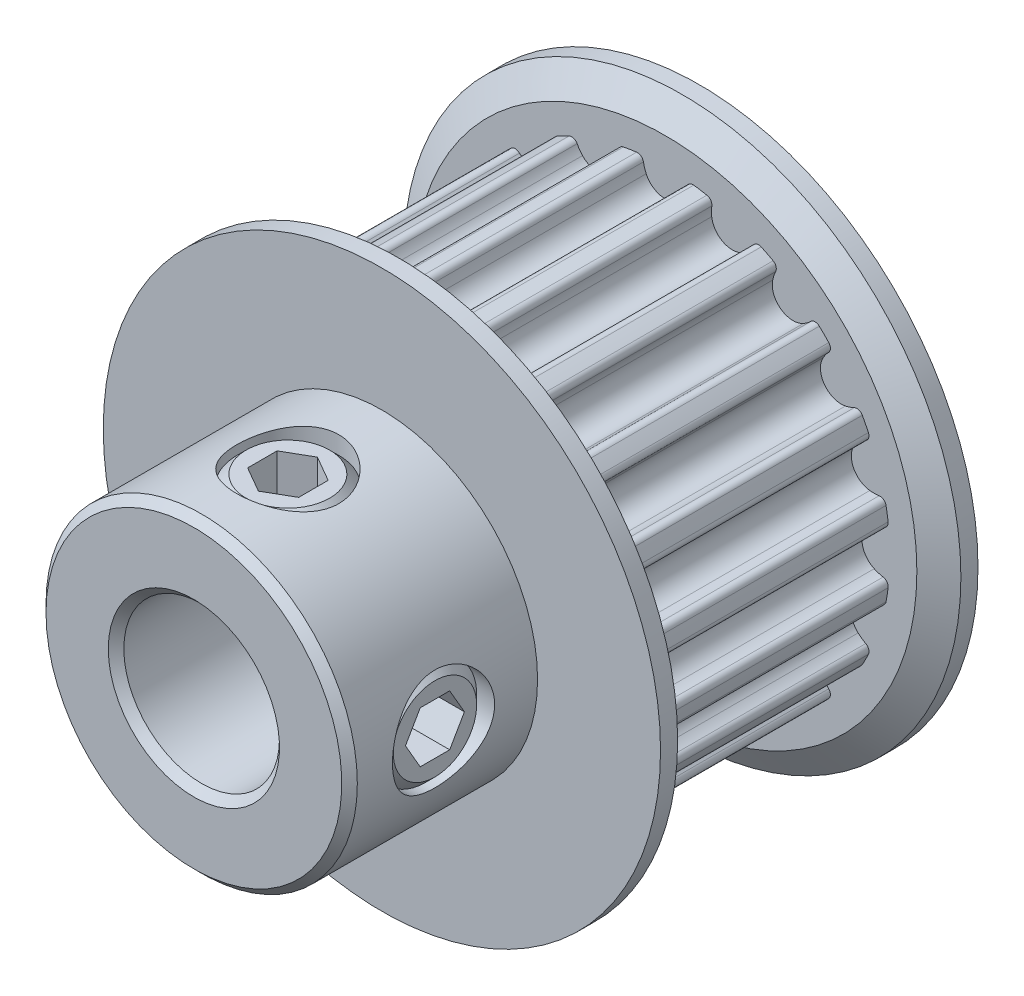
SolidWorks part; units mm, degrees
ref_plane "Front Plane" through (0, 0, 0) normal (0, 0, 1) x (1, 0, 0)
ref_plane "Top Plane" through (0, 0, 0) normal (0, 1, 0) x (1, 0, 0)
ref_plane "Right Plane" through (0, 0, 0) normal (1, 0, 0) x (0, 0, -1)
sketch "Sketch1" plane through (0, 0, 0) normal (0, 0, 1) x (1, 0, 0)
  line L1 (-2.6202, 8.0295) -> (2.6202, 8.0295) construction
  line L4 (0, 0) -> (0, 8.0295) construction
  line L5 (0, 8.0295) -> (0, 13.7072) construction
  line L6 (0, 9.5505) -> (2.9628, 9.0793) construction
  line L7 (2.9628, 9.0793) -> (4.0126, 8.7367) construction
  line L8 (2.9628, 9.0793) -> (2.6202, 8.0295) construction
  line L9 (-2.9628, 9.0793) -> (-2.6202, 8.0295) construction
  line L10 (-2.8446, 8.7171) -> (-3.7091, 11.3665)
  line L11 (-3.7091, 11.3665) -> (3.7091, 11.3665)
  line L12 (3.7091, 11.3665) -> (2.8446, 8.7171)
  circle A0 centre (0, 0) radius 9.5505 construction
  circle A1 centre (0, 0) radius 11.3665 construction
  circle A2 centre (0, 0) radius 9.1695 construction
  arc A3 (-0.7739, 8.5279) -> (0.7739, 8.5279) centre (0, 8.8795) ccw
  arc A4 (-0.7739, 8.5279) -> (-0.8866, 8.891) centre (0.61, 9.1566) cw
  arc A5 (-2.8446, 8.7171) -> (-1.1645, 9.0953) centre (0, 0) cw
  arc A6 (-0.8866, 8.891) -> (-1.1645, 9.0953) centre (-1.1328, 8.8473) ccw
  arc A7 (2.8446, 8.7171) -> (1.1645, 9.0953) centre (0, 0) ccw
  arc A8 (0.8866, 8.891) -> (1.1645, 9.0953) centre (1.1328, 8.8473) cw
  arc A9 (0.7739, 8.5279) -> (0.8866, 8.891) centre (-0.61, 9.1566) ccw
  point P6 (0, 20.9083)
  point P11 (0, 9.5505)
  point P13 (0, 11.3665)
  point P14 (0, 9.1695)
  dimension "D1" = 7.2012
  dimension "D2" = 4.1567
sketch "Sketch2" plane through (0, 0, 0) normal (1, 0, 0) x (0, 0, -1)
  line L0 (-10.31, 3.175) -> (10.31, 3.175)
  line L1 (-10.31, 3.175) -> (-10.31, 6.35)
  line L2 (-10.31, 6.35) -> (-2.64, 6.35)
  line L3 (-2.64, 6.35) -> (-2.64, 11.3665)
  line L4 (-2.64, 11.3665) -> (-1.245, 11.3665) construction
  line L5 (-1.245, 11.3665) -> (-1.245, 9.1695) construction
  line L6 (-1.245, 9.1695) -> (8.915, 9.1695)
  line L7 (8.915, 9.1695) -> (8.915, 11.3665) construction
  line L8 (8.915, 11.3665) -> (10.31, 11.3665) construction
  line L9 (10.31, 11.3665) -> (10.31, 3.175)
  line L10 (-10.31, 0) -> (10.31, 0) construction
  line L11 (9.6125, 11.3665) -> (8.915, 10.268)
  line L12 (-1.245, 10.268) -> (-1.9425, 11.3665)
  line L13 (-2.64, 11.3665) -> (-1.9425, 11.3665)
  line L14 (-1.245, 10.268) -> (-1.245, 9.1695)
  line L15 (8.915, 9.1695) -> (8.915, 10.268)
  line L16 (9.6125, 11.3665) -> (10.31, 11.3665)
  arc A0 (-1.245, 10.268) -> (-1.9425, 11.3665) centre (-2.4588, 10.268) ccw construction
  arc A1 (8.915, 10.268) -> (9.6125, 11.3665) centre (10.1288, 10.268) cw construction
  point P12 (-1.245, 10.268)
  point P14 (-1.9425, 11.3665)
  point P20 (8.915, 10.268)
  point P21 (9.6125, 11.3665)
  point P25 (8.915, 0)
  point P26 (-1.245, 0)
revolve "Revolve1" add sketch "Sketch2" angle 360 mid plane about L10
sketch "Sketch3" plane through (0, 0, 0) normal (0, 0, 1) x (1, 0, 0)
  line L6 (3.7091, 11.3665) -> (-3.7091, 11.3665)
  line L7 (2.8446, 8.7171) -> (3.7091, 11.3665)
  line L8 (-3.7091, 11.3665) -> (-2.8446, 8.7171)
  line L9 (3.7091, 11.3665) -> (-3.7091, 11.3665)
  line L10 (2.8446, 8.7171) -> (3.7091, 11.3665)
  line L11 (-3.7091, 11.3665) -> (-2.8446, 8.7171)
  arc A8 (2.8446, 8.7171) -> (1.1645, 9.0953) centre (0, 0) ccw
  arc A9 (1.1645, 9.0953) -> (0.8866, 8.891) centre (1.1328, 8.8473) ccw
  arc A10 (0.7739, 8.5279) -> (0.8866, 8.891) centre (-0.61, 9.1566) ccw
  arc A11 (-0.7739, 8.5279) -> (0.7739, 8.5279) centre (0, 8.8795) ccw
  arc A12 (-0.8866, 8.891) -> (-0.7739, 8.5279) centre (0.61, 9.1566) ccw
  arc A13 (-0.8866, 8.891) -> (-1.1645, 9.0953) centre (-1.1328, 8.8473) ccw
  arc A14 (-1.1645, 9.0953) -> (-2.8446, 8.7171) centre (0, 0) ccw
  arc A15 (2.8446, 8.7171) -> (1.1645, 9.0953) centre (0, 0) ccw
  arc A16 (1.1645, 9.0953) -> (0.8866, 8.891) centre (1.1328, 8.8473) ccw
  arc A17 (0.7739, 8.5279) -> (0.8866, 8.891) centre (-0.61, 9.1566) ccw
  arc A18 (-0.7739, 8.5279) -> (0.7739, 8.5279) centre (0, 8.8795) ccw
  arc A19 (-0.8866, 8.891) -> (-0.7739, 8.5279) centre (0.61, 9.1566) ccw
  arc A20 (-0.8866, 8.891) -> (-1.1645, 9.0953) centre (-1.1328, 8.8473) ccw
  arc A21 (-1.1645, 9.0953) -> (-2.8446, 8.7171) centre (0, 0) ccw
  dimension "D1" = 0
extrude "Cut-Extrude1" cut sketch "Sketch3" against normal up to vertex (8.915 mm away) from vertex up to point (0, 9.1695, -8.915) starting at point (0, 9.1695, 1.245)
pattern_circular "CirPattern1" count 20 over 360 about axis through (0, 0, 10.31) along (0, 0, 1) of "Cut-Extrude1"
sketch "Sketch4" plane through (0, 0, 0) normal (1, 0, 0) x (0, -1, 0)
  line L0 (0, -2.64) -> (0, -10.31) construction
  line L1 (-6.35, -2.64) -> (6.35, -2.64) construction
  line L2 (-6.35, -10.31) -> (6.35, -10.31) construction
  circle A0 centre (0, -6.475) radius 2.0828
extrude "Cut-Extrude2" cut sketch "Sketch4" along normal through all
ref_plane "Plane1" through (0, 0, 6.475) normal (0, 0, 1) x (1, 0, 0)
sketch "Sketch5" plane through (0, 0, 6.475) normal (0, 0, 1) x (1, 0, 0)
  line L0 (0, 0.1664) -> (0, 6.35) construction
  line L1 (3.175, -1.7018) -> (3.175, 0)
  line L2 (3.556, -2.0828) -> (5.6177, -2.0828)
  line L3 (3.175, 0) -> (6.35, 0) construction
  line L4 (3.175, 0) -> (5.9987, 0)
  line L5 (5.9987, 0) -> (5.9987, -1.7018)
  line L6 (3.556, -2.0828) -> (3.175, -1.7018)
  line L7 (5.9987, -1.7018) -> (5.6177, -2.0828)
  circle A0 centre (0, 0) radius 6.35 construction
  circle A1 centre (0, 0) radius 3.175 construction
  point P2 (3.175, -2.0828)
  point P11 (5.9987, -2.0828)
revolve "Revolve2" add sketch "Sketch5" angle 360 mid plane about L4
sketch "Sketch6" plane through (5.9987, 5.3841, 0) normal (-1, 0, 0) x (0, -1, 0)
  line L1 (5.3841, 7.6775) -> (4.3427, 7.0763)
  line L2 (4.3427, 7.0763) -> (4.3427, 5.8737)
  line L3 (4.3427, 5.8737) -> (5.3841, 5.2725)
  line L4 (5.3841, 5.2725) -> (6.4255, 5.8737)
  line L5 (6.4255, 5.8737) -> (6.4255, 7.0763)
  line L6 (6.4255, 7.0763) -> (5.3841, 7.6775)
  circle A0 centre (5.3841, 6.475) radius 1.0414 construction
  dimension "D1" = 2.0828
extrude "Cut-Extrude3" cut sketch "Sketch6" along normal blind 1.5621
pattern_circular "CirPattern2" count 2 over 90 about axis through (0, 0, 10.31) along (0, 0, 1) of "Cut-Extrude2", "Revolve2", "Cut-Extrude3"
chamfer "Chamfer1" distance 0.3175 angle 45 2 edges at (3.175, 0, 10.31) (6.35, 0, 10.31)
ref_axis "Center Axis 1" through (0, 0, -10.31) along (0, 0, 1)
ref_plane "Contact Plane 1" through (0, 0, 10.31) normal (0, 0, 1) x (1, 0, 0)
ref_plane "Contact Plane 2" through (0, 0, -10.31) normal (0, 0, -1) x (-1, 0, 0)
equation "\"D2@Sketch1\" = \"D1@Sketch1\"/2"
equation "\"D1@Sketch6\" = \"Set Screw@Sketch4\" / 2"
equation "\"D1@Cut-Extrude3\" = \"D1@Sketch6\"*.75"
equation "\"D1@Chamfer1\"=\"Hub Dia@Sketch2\"*.025"
